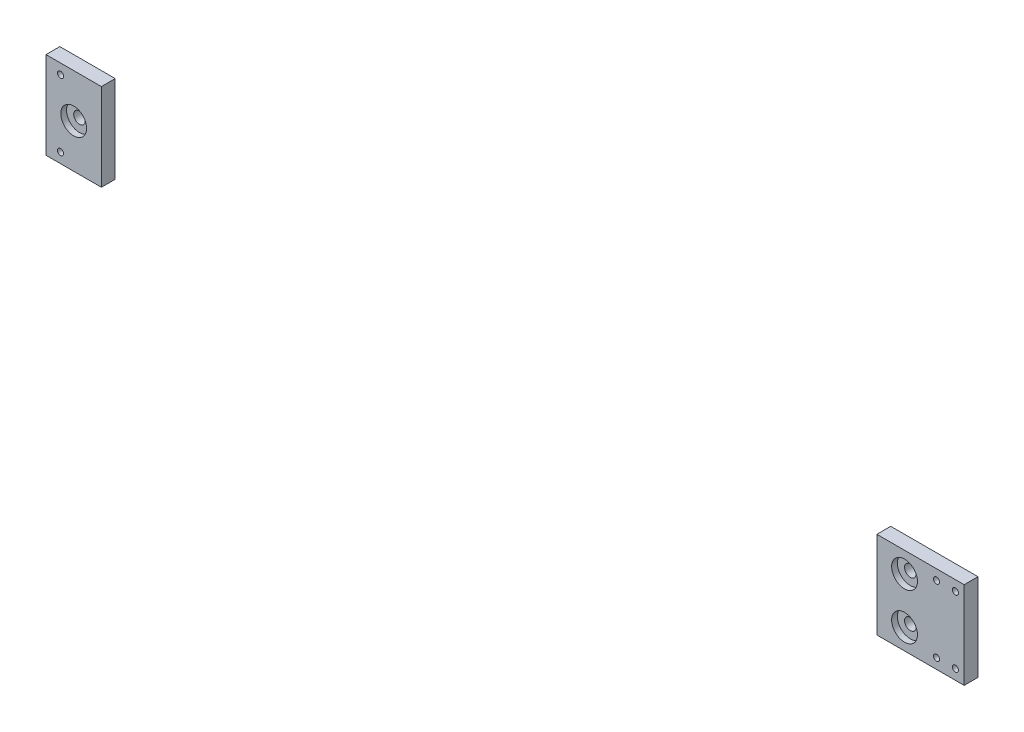
SolidWorks part; units mm, degrees
other "Rear Bracket"
other "Front Bracket"
ref_plane "Front Plane" through (0, 0, 0) normal (0, 0, 1) x (1, 0, 0)
ref_plane "Top Plane" through (0, 0, 0) normal (0, 1, 0) x (1, 0, 0)
ref_plane "Right Plane" through (0, 0, 0) normal (1, 0, 0) x (0, 0, -1)
sketch "Sketch2" plane through (0, 0, 0) normal (0, 0, 1) x (1, 0, 0)
  line L0 (304.725, 30) -> (276.237, 30)
  line L1 (-295.275, -30) -> (-257.175, -30)
  line L2 (-295.275, -30) -> (-295.275, 30)
  line L3 (-295.275, 30) -> (-257.175, 30)
  line L4 (-257.175, -30) -> (-257.175, 30)
  line L5 (-295.275, -30) -> (-257.175, 30) construction
  line L6 (-295.275, 30) -> (-257.175, -30) construction
  line L7 (304.725, -30) -> (342.825, -30)
  line L8 (304.725, -30) -> (304.725, 30) construction
  line L9 (304.725, 30) -> (342.825, 30)
  line L10 (342.825, -30) -> (342.825, 30)
  line L11 (304.725, -30) -> (342.825, 30) construction
  line L12 (304.725, 30) -> (342.825, -30) construction
  line L13 (276.237, -152.388) -> (276.237, 152.412) construction
  line L14 (276.237, 30) -> (276.237, -30)
  line L15 (276.237, -30) -> (304.725, -30)
  circle A0 centre (-276.225, 0) radius 3.9688
  circle A1 centre (-276.225, 0) radius 8.89
  circle A2 centre (323.775, 0) radius 3.9688 construction
  circle A3 centre (323.775, 0) radius 8.89 construction
  point P0 (-276.225, 0)
  point P9 (323.775, 0)
  dimension "D3" = 17.78
  dimension "D4" = 7.9375
  dimension "D1" = 38.1
  dimension "D2" = 60
  dimension "D6" = 600
  dimension "D5" = 2
extrude "Main Extrusion" add sketch "Sketch2" along normal blind 5.5575 contours L1 L4 L3 L2 A1 | A1 A0 | L7 L10 L9 L8 A3 | A3 A2 region at (309.531, 0, 0) region at (-294.5643, 0, 0) region at (-284.8636, 0, 0)
extrude "Counterbore extrusion" add sketch "Sketch2<3>" along normal blind 9.525 contours L1 L4 L3 L2 A1 | L7 L10 L9 L8 A3 region at (309.531, 0, 0) region at (-294.5643, 0, 0)
sketch "Sketch2<3>" plane through (0, 0, 0) normal (0, 0, 1) x (1, 0, 0) same geometry as "Sketch2"
sketch "Sketch3" plane through (0, 0, 9.525) normal (0, 0, 1) x (1, 0, 0)
  line L0 (-295.275, 0) -> (-257.175, 0) construction
  line L2 (-257.175, -30) -> (-257.175, 30) construction
  circle A0 centre (-285.275, 23) radius 2.1
  circle A1 centre (-285.275, -23) radius 2.1
  point P6 (-276.225, 0)
  dimension "D1" = 4.2
  dimension "D2" = 46
  dimension "D3" = 10
extrude "M5 Threaded holse for front bracket" cut sketch "Sketch3" against normal up to surface (9.525 mm away) up to face at (-272.2562, 0, 0)
sketch "Sketch5" plane through (0, 0, 9.525) normal (0, 0, 1) x (1, 0, 0)
  line L0 (317.275, 23) -> (330.275, 23) construction
  line L1 (317.275, 23) -> (317.275, -23) construction
  circle A0 centre (317.275, 23) radius 2.1
  circle A1 centre (330.275, 23) radius 2.1
  circle A2 centre (330.275, -23) radius 2.1
  circle A3 centre (317.275, -23) radius 2.1
  point P0 (323.775, 0)
  point P5 (323.775, 23)
  point P6 (317.275, 0)
  dimension "D6" = 4.2
  dimension "D3" = 90
  dimension "D4" = 13
  dimension "D5" = 46
  dimension "D1" = 2
  dimension "D2" = 2
extrude "M5 Threaded holes for bracket" cut sketch "Sketch5" against normal up to surface (9.525 mm away) up to face at (309.531, 0, 0)
sketch "Sketch6" plane through (0, 0, 9.525) normal (0, 0, 1) x (1, 0, 0)
  line L0 (295.275, -171.45) -> (295.275, 171.45) construction
  line L1 (295.275, -171.45) -> (295.275, 171.45) construction
  line L2 (13.75, 0) -> (-13.75, 0) construction
  circle A0 centre (295.275, 15.875) radius 8.89
  circle A1 centre (295.275, 15.875) radius 3.9688
  circle A2 centre (323.775, 0) radius 8.89 construction
  circle A3 centre (323.775, 0) radius 3.9688 construction
  circle A4 centre (295.275, -15.875) radius 3.9688
  circle A5 centre (295.275, -15.875) radius 8.89
  dimension "D1" = 31.75
extrude "centre bore" cut sketch "Sketch6" against normal through all contours L1 A1 | A1 L1 | L1 A4 | A4 L1 region at (293.5906, -15.875, 9.525) region at (296.9594, -15.875, 9.525) region at (293.5906, 15.875, 9.525) region at (296.9594, 15.875, 9.525)
extrude "counterbore" cut sketch "Sketch6<3>" against normal offset from surface (3.9675 mm away) 5.5575 up to face at (309.531, 0, 0)
sketch "Sketch6<3>" plane through (0, 0, 9.525) normal (0, 0, 1) x (1, 0, 0) same geometry as "Sketch6"
sketch "Sketch7" plane through (0, 0, 9.525) normal (0, 0, 1) x (1, 0, 0)
  line L1 (342.825, 30) -> (336.275, 30)
  line L2 (342.825, 30) -> (342.825, -30)
  line L3 (342.825, -30) -> (336.275, -30)
  line L4 (336.275, 30) -> (336.275, -30)
extrude "stupid cut" cut sketch "Sketch7" against normal through all
